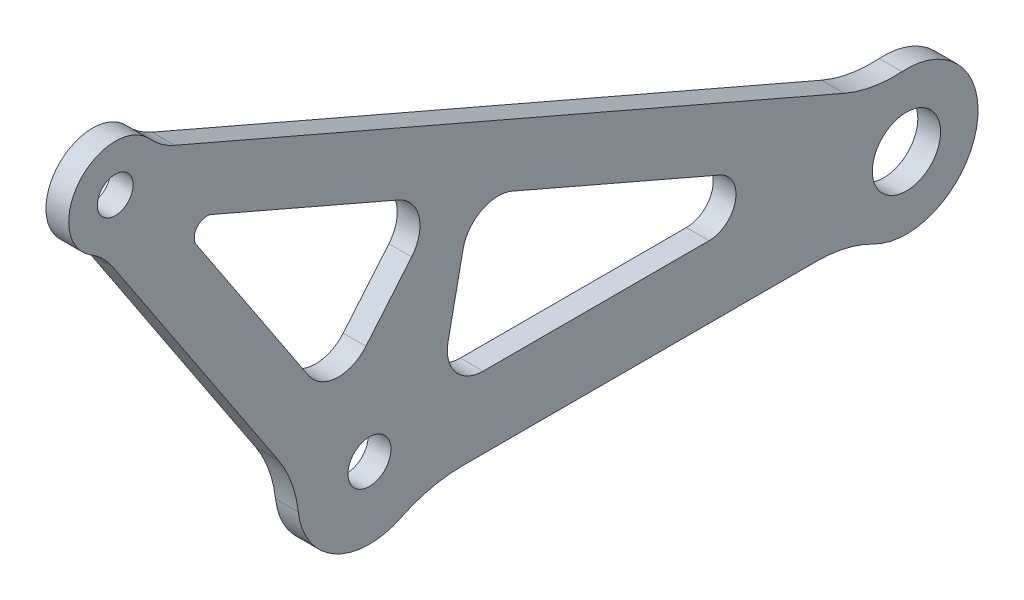
SolidWorks part; units mm, degrees
material "AISI 1020"
ref_plane "Front Plane" through (0, 0, 0) normal (0, 0, 1) x (1, 0, 0)
ref_plane "Top Plane" through (0, 0, 0) normal (0, 1, 0) x (1, 0, 0)
ref_plane "Right Plane" through (0, 0, 0) normal (1, 0, 0) x (0, 0, -1)
sketch "Sketch1" plane through (0, 0, 0) normal (1, 0, 0) x (0, 0, -1)
  line L0 (-60.7171, 0) -> (60.7171, 0)
  line L3 (0, -143.7223) -> (0, 143.7223) construction
  line L4 (-149.7529, 101.5535) -> (-94.5581, 18.1812)
  line L5 (-134.4049, 119.8783) -> (67.4524, 32.5212)
  line L6 (-75, 14) -> (75, 14) construction
  line L8 (-146, 114) -> (-75, 14) construction
  arc A20 (-134.4049, 119.8783) -> (-149.7529, 101.5535) centre (-146, 114) ccw
  arc A22 (-94.5581, 18.1812) -> (-60.7171, 0) centre (-75, 14) ccw
  arc A23 (60.7171, 0) -> (67.4524, 32.5212) centre (75, 14) ccw
  point P5 (0, 0)
  point P14 (0, 0)
  dimension "D3" = 20
  dimension "D5" = 13
  dimension "D6" = 20
  dimension "D4" = 127
  dimension "D7" = 254
  dimension "D10" = 6
  dimension "D11" = 6
  dimension "D9" = 3
  dimension "D12" = 3
  dimension "D13" = 6
  dimension "D14" = 6
  dimension "D2" = 150
  dimension "D8" = 122.6418
extrude "Boss-Extrude1" add sketch "Sketch1" along normal blind 6.35
hole_wizard "3/4 (0.75) Diameter Hole1" positions "Sketch4" profile "Sketch3" hole size "3/4" standard "ANSI Inch" end condition up to next
sketch "Sketch4" plane through (6.35, 0, 0) normal (1, 0, 0) x (0, 0, -1)
  point P5 (75, 14)
sketch "Sketch3" plane through (6.35, 14, -75) normal (0, 1, 0) x (0, 0, -1)
  line L0 (0, 0) -> (0, 6.35)
  line L1 (0, 6.35) -> (9.525, 6.35)
  line L2 (9.525, 6.35) -> (9.525, 0)
  line L5 (9.525, 0) -> (0, 0)
  line L11 (0, -6.35) -> (0, 107.95) construction
  dimension "Thru Hole Dia." = 19.05
  dimension "Thru Hole Depth" = 6.35
hole_wizard "Ø10.0 (10) Diameter Hole1" positions "Sketch9" profile "Sketch6" hole size "Ø10.0" standard "ANSI Metric" end condition up to next
sketch "Sketch9" plane through (6.35, 0, 0) normal (1, 0, 0) x (0, 0, -1)
  point P0 (-146, 114)
sketch "Sketch6" plane through (6.35, 114, 146) normal (0, 1, 0) x (0, 0, -1)
  line L0 (0, 0) -> (0, 6.35)
  line L1 (0, 6.35) -> (5, 6.35)
  line L2 (5, 6.35) -> (5, 0)
  line L5 (5, 0) -> (0, 0)
  line L11 (0, -6.35) -> (0, 107.95) construction
  dimension "Thru Hole Dia." = 10
  dimension "Thru Hole Depth" = 6.35
hole_wizard "Ø12.0 (12) Diameter Hole2" positions "Sketch15" profile "Sketch11" hole size "Ø12.0" standard "ANSI Metric" end condition up to next
sketch "Sketch15" plane through (6.35, 0, 0) normal (1, 0, 0) x (0, 0, -1)
  line L0 (75, 14) -> (157.5513, 156.983)
  line L2 (0, 0) -> (0, 108.153) construction
  line L4 (-146, 114) -> (-119.4521, 194.8786)
  line L6 (-174.545, 70.324) -> (-178.0536, 59.6351) construction
  line L7 (-174.545, 70.324) -> (-178.0536, 59.6351) construction
  arc A0 (-94.5581, 18.1812) -> (-60.7171, 0) centre (-75, 14) ccw construction
  point P0 (-75, 14)
  dimension "D1" = 30
sketch "Sketch11" plane through (6.35, 14, 75) normal (0, 1, 0) x (0, 0, -1)
  line L0 (0, 0) -> (0, 6.35)
  line L1 (0, 6.35) -> (6, 6.35)
  line L2 (6, 6.35) -> (6, 0)
  line L5 (6, 0) -> (0, 0)
  line L11 (0, -6.35) -> (0, 107.95) construction
  dimension "Thru Hole Dia." = 12
  dimension "Thru Hole Depth" = 6.35
sketch "Sketch8" plane through (6.35, 0, 0) normal (1, 0, 0) x (0, 0, -1)
  line L2 (-54.6038, 67.909) -> (-46.3441, 64.3345) construction
  line L3 (-53.0348, 32.028) -> (-48.8351, 52.3065)
  line L7 (-75.9833, 42.3827) -> (-63.2097, 57.6339)
  line L9 (-123.3455, 90.6494) -> (-91.9879, 43.2834)
  line L10 (-119.037, 95.7935) -> (-66.9043, 73.2322)
  line L11 (19.8861, 20) -> (-43.2426, 20)
  line L12 (67.4524, 32.5212) -> (-134.4049, 119.8783) construction
  line L13 (-149.7529, 101.5535) -> (-94.5581, 18.1812) construction
  line L14 (-60.7171, 0) -> (60.7171, 0) construction
  line L15 (-84.5892, 32.1076) -> (-83.2072, 30.0201) construction
  line L16 (-55.5259, 20) -> (-58.0294, 20) construction
  line L17 (-54.6038, 67.909) -> (-46.3441, 64.3345) construction
  line L18 (-35.0712, 59.4559) -> (22.8649, 34.3831)
  line L19 (-120.4271, 92.5814) -> (-104.3957, 79.1543) construction
  line L20 (19.8861, 27.5) -> (27.9693, 25.826) construction
  line L21 (-29.8567, 10) -> (10.3311, 10) construction
  arc A0 (-53.0348, 32.028) -> (-43.2426, 20) centre (-43.2426, 30) ccw
  arc A2 (-48.8351, 52.3065) -> (-35.0712, 59.4559) centre (-39.0429, 50.2785) cw
  arc A4 (-63.2097, 57.6339) -> (-66.9043, 73.2322) centre (-70.876, 64.0548) ccw
  arc A14 (-119.037, 95.7935) -> (-123.3455, 90.6494) centre (-120.4271, 92.5814) ccw
  arc A20 (-75.9833, 42.3827) -> (-91.9879, 43.2834) centre (-83.6496, 48.8036) cw
  arc A25 (-134.4049, 119.8783) -> (-149.7529, 101.5535) centre (-146, 114) ccw construction
  circle A27 centre (-146, 114) radius 5 construction
  arc A36 (-94.5581, 18.1812) -> (-60.7171, 0) centre (-75, 14) ccw construction
  circle A39 centre (-75, 14) radius 6 construction
  arc A40 (19.8861, 20) -> (22.8649, 34.3831) centre (19.8861, 27.5) ccw
  circle A54 centre (-75, 14) radius 18
  arc A55 (-58.0294, 20) -> (-83.2072, 30.0201) centre (-75, 14) ccw construction
  point P7 (-33.5049, 66.1162)
  point P19 (-33.4763, 76.1997)
  dimension "D8" = 8
  dimension "D9" = 14
  dimension "D11" = 9
  dimension "D7" = 4
  dimension "D1" = 7
  dimension "D10" = 24.8576
  dimension "D2" = 15
  dimension "D12" = 10
  dimension "D13" = 14.6862
  dimension "D3" = 12
  dimension "D5" = 16
  dimension "D6" = 20
  dimension "D4" = 16
extrude "Cut-Extrude1" cut sketch "Sketch8" against normal up to next
fillet "Fillet1" radius 35 1 edges at (3.175, 18.1812, 94.5581)
fillet "Fillet3" radius 35 2 edges at (3.175, 32.5212, -67.4524) (3.175, 0, -60.7171)
fillet "Fillet4" radius 20 2 edges at (3.175, 101.5535, 149.7529) (3.175, 119.8783, 134.4049)
fillet "Fillet6" radius 40 1 edges at (3.175, 0, 60.7171)
equation "\"D11@Sketch1\"=\"D10@Sketch1\""
equation "\"D12@Sketch1\"=\"D9@Sketch1\""
equation "\"D14@Sketch1\"=\"D13@Sketch1\""
